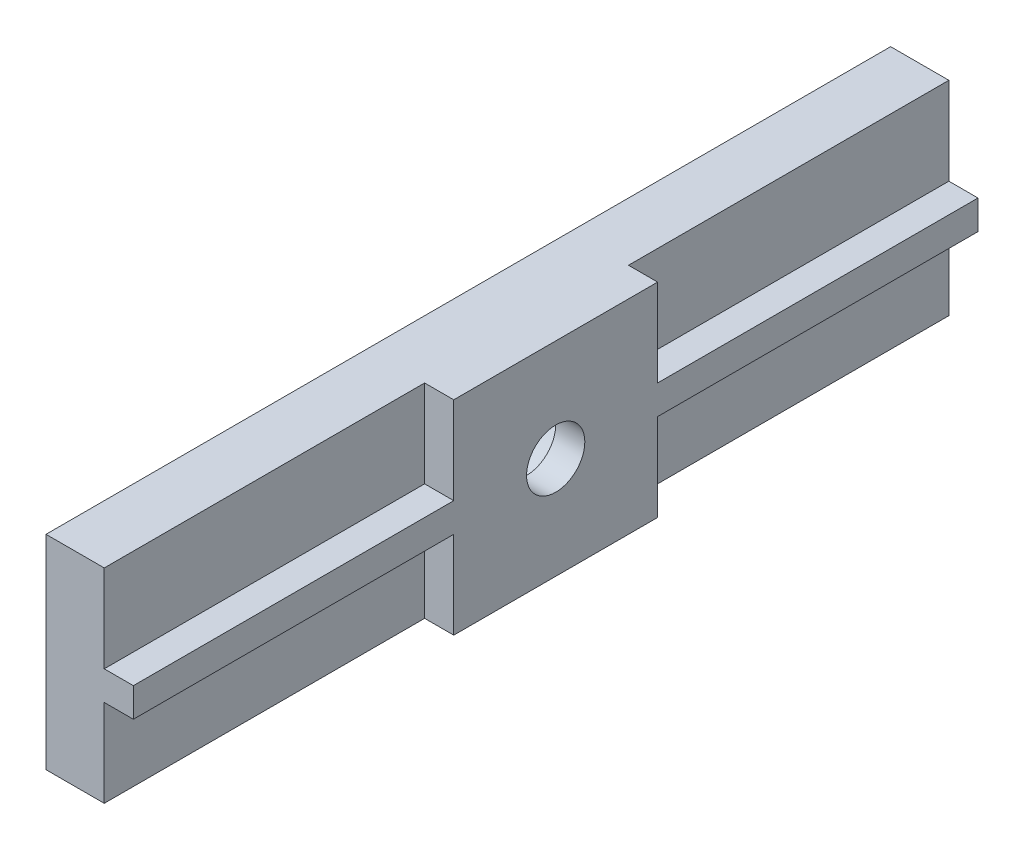
SolidWorks part; units mm, degrees
ref_plane "Front Plane" through (0, 0, 0) normal (0, 0, 1) x (1, 0, 0)
ref_plane "Top Plane" through (0, 0, 0) normal (0, 1, 0) x (1, 0, 0)
ref_plane "Right Plane" through (0, 0, 0) normal (1, 0, 0) x (0, 0, -1)
sketch "Sketch2" plane through (0, 0, 0) normal (1, 0, 0) x (0, 0, -1)
  line L1 (-92.075, -22.225) -> (92.075, -22.225)
  line L2 (-92.075, -22.225) -> (-92.075, 22.225)
  line L3 (-92.075, 22.225) -> (92.075, 22.225)
  line L4 (92.075, -22.225) -> (92.075, 22.225)
  line L5 (-92.075, -22.225) -> (92.075, 22.225) construction
  line L6 (-92.075, 22.225) -> (92.075, -22.225) construction
  line L7 (-22.225, -22.225) -> (22.225, -22.225)
  line L8 (-22.225, -22.225) -> (-22.225, 22.225)
  line L9 (-22.225, 22.225) -> (22.225, 22.225)
  line L10 (22.225, -22.225) -> (22.225, 22.225)
  line L11 (-22.225, -22.225) -> (22.225, 22.225) construction
  line L12 (-22.225, 22.225) -> (22.225, -22.225) construction
  line L13 (-92.075, -3.175) -> (92.075, -3.175)
  line L14 (-92.075, -3.175) -> (-92.075, 3.175)
  line L15 (-92.075, 3.175) -> (92.075, 3.175)
  line L16 (92.075, -3.175) -> (92.075, 3.175)
  line L17 (-92.075, -3.175) -> (92.075, 3.175) construction
  line L18 (-92.075, 3.175) -> (92.075, -3.175) construction
  circle A0 centre (0, 0) radius 6.35
  point P0 (0, 0)
  point P6 (0, 0)
  point P11 (0, 0)
  dimension "D5" = 12.7
  dimension "D1" = 184.15
  dimension "D2" = 44.45
  dimension "D3" = 44.45
  dimension "D4" = 6.35
extrude "Boss-Extrude1" add sketch "Sketch2" along normal blind 6.35 contours A0 L15 L10 L3 L8 | A0 L13 L8 L1 L10 | L15 L2 L13 L8 | A0 L13 L10 L15 | A0 L15 L8 L13 | L15 L10 L13 L4 region at (0, -12.9477, 0) region at (0, 0, 57.15) region at (0, 0, 14.1478) region at (0, 0, -14.1478) region at (0, 0, -57.15) region at (0, 12.9477, 0)
extrude "Boss-Extrude2" add sketch "Sketch2<3>" against normal blind 12.7 contours L15 A0 | L15 A0 L13 | L13 A0 | L3 L4 L1 L2 region at (0, 0, 0) region at (0, -4.4769, 0) region at (0, 4.4769, 0)
sketch "Sketch2<3>" plane through (0, 0, 0) normal (1, 0, 0) x (0, 0, -1) same geometry as "Sketch2"
sketch "Sketch3" plane through (-12.7, 0, 0) normal (-1, 0, 0) x (0, 0, 1)
  circle A0 centre (0, 0) radius 17.4625
  dimension "D1" = 34.925
extrude "Cut-Extrude1" cut sketch "Sketch3" against normal blind 12.7
